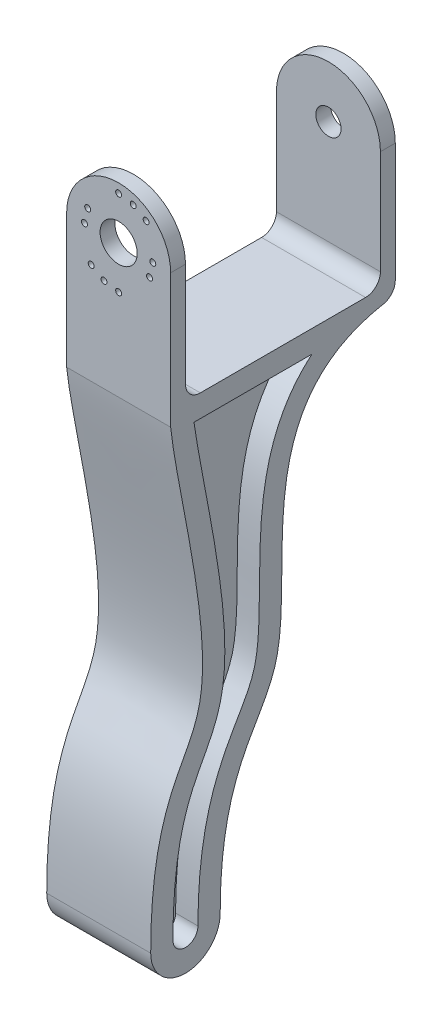
SolidWorks part; units mm, degrees
material "ABS"
ref_plane "Front Plane" through (0, 0, 0) normal (0, 0, 1) x (1, 0, 0)
ref_plane "Top Plane" through (0, 0, 0) normal (0, 1, 0) x (1, 0, 0)
ref_plane "Right Plane" through (0, 0, 0) normal (1, 0, 0) x (0, 0, -1)
sketch "Sketch1" plane through (0, 0, 0) normal (0, 1, 0) x (1, 0, 0)
  line L1 (0, 0) -> (-17.78, 0)
  line L2 (0, 0) -> (0, -33.3375)
  line L3 (0, -33.3375) -> (-17.78, -33.3375)
  line L4 (-17.78, 0) -> (-17.78, -33.3375)
  dimension "D1" = 17.78
  dimension "D2" = 33.3375
extrude "Boss-Extrude1" add sketch "Sketch1" along normal blind 2.54
sketch "Sketch2" plane through (0, 0, 33.3375) normal (0, 0, 1) x (1, 0, 0)
  line L0 (-17.78, 0) -> (0, 0) construction
  line L1 (-17.78, 2.54) -> (-17.78, 0) construction
  line L2 (-17.78, 0) -> (0, 0)
  line L3 (-17.78, 2.54) -> (-17.78, 0)
  line L4 (-17.78, 2.54) -> (-17.78, 22.86)
  line L5 (0, 22.86) -> (0, 2.54)
  line L6 (-17.78, 2.54) -> (0, 2.54) construction
  line L7 (-8.89, 30.1625) -> (-6.3887, 29.7208) construction
  line L8 (-6.3887, 29.7208) -> (-4.19, 28.449) construction
  line L9 (-3.048, 22.86) -> (-3.6002, 20.3807) construction
  line L10 (-8.89, 15.5575) -> (-11.3913, 15.9992) construction
  line L11 (-13.59, 17.271) -> (-11.3913, 15.9992) construction
  line L12 (-14.732, 22.86) -> (-14.1798, 25.3393) construction
  line L13 (0, 2.54) -> (0, 0)
  circle A0 centre (-8.89, 22.86) radius 8.89
  circle A1 centre (-8.89, 22.86) radius 8.89 construction
  circle A2 centre (-8.89, 22.86) radius 3.175
  circle A3 centre (-8.89, 22.86) radius 7.3025 construction
  circle A4 centre (-8.89, 22.86) radius 5.842 construction
  circle A5 centre (-8.89, 30.1625) radius 0.508
  circle A6 centre (-6.3887, 29.7208) radius 0.508
  circle A7 centre (-4.19, 28.449) radius 0.508
  circle A8 centre (-8.89, 15.5575) radius 0.508
  circle A9 centre (-11.3913, 15.9992) radius 0.508
  circle A10 centre (-13.59, 17.271) radius 0.508
  circle A11 centre (-3.048, 22.86) radius 0.508
  circle A12 centre (-3.6002, 20.3807) radius 0.508
  circle A13 centre (-14.732, 22.86) radius 0.508
  circle A14 centre (-14.1798, 25.3393) radius 0.508
  point P9 (-8.89, 2.54)
  line M3 (-17.78, 0) -> (0, 0)
  line M4 (0, 0) -> (0, 2.54)
  line M5 (0, 2.54) -> (-17.78, 2.54)
  line M6 (-17.78, 2.54) -> (-17.78, 0)
  dimension "D1" = 17.78
  dimension "D4" = 11.684
  dimension "D5" = 1.016
  dimension "D6" = 14.605
  dimension "D7" = 6.35
  dimension "D2" = 20.32
  dimension "D3" = 2.54
extrude "Boss-Extrude2" add sketch "Sketch2" along normal blind 2.54 contours A0 L4 M5 M4 | A0 | M6 M3 M4 M5 region at (-8.89, 1.27, 33.3375) region at (-8.89, 9.3565, 33.3375) region at (-8.89, 31.4986, 33.3375)
sketch "Sketch3" plane through (0, 0, 0) normal (0, 0, -1) x (-1, 0, 0)
  line L3 (0, 22.86) -> (0, 0)
  line L4 (17.78, 0) -> (17.78, 22.86)
  line L5 (0, 22.86) -> (0, 0)
  line L6 (0, 0) -> (17.78, 0)
  line L8 (17.78, 0) -> (17.78, 22.86)
  line L10 (0, 0) -> (17.78, 0)
  circle A0 centre (8.89, 22.86) radius 2.159
  arc A1 (17.78, 22.86) -> (0, 22.86) centre (8.89, 22.86) ccw
  arc A2 (17.78, 22.86) -> (0, 22.86) centre (8.89, 22.86) ccw
  dimension "D2" = 4.318
  dimension "D1" = 0
extrude "Boss-Extrude3" add sketch "Sketch3" along normal blind 2.54
sketch "Sketch7" plane through (-17.78, 0, 0) normal (-1, 0, 0) x (0, 0, 1)
  line L0 (-2.54, 0) -> (35.8775, 0) construction
  line L1 (-0.2642, 0) -> (35.8775, 0)
  arc A0 (39.2853, -76.2) -> (27.3979, -76.2) centre (33.3416, -76.2) cw
  spline S0 degree 3 poles (35.8775, 0) (34.7476, -10.4834) (23.9939, -49.6564) (39.2853, -53.149) (39.2853, -76.2) knots 0 0 0 0 0.561591 1 1 1 1
  spline S1 degree 3 poles (-0.2642, 0) (22.6993, -4.421) (9.1079, -48.9083) (27.3979, -54.2744) (27.3979, -76.2) knots 0 0 0 0 0.588388 1 1 1 1
  point P5 (16.5148, -21.1478)
  point P8 (17.7426, -43.2288)
  dimension "D1" = 76.2
extrude "Boss-Extrude5" add sketch "Sketch7" against normal up to vertex (17.78 mm away) up to point (0, 0, -2.54)
sketch "Sketch8" plane through (-17.78, 0, 0) normal (-1, 0, 0) x (0, 0, 1)
  line L14 (31.88, -1.27) -> (11.6921, -1.27)
  line L15 (31.88, -1.27) -> (11.6921, -1.27)
  arc A2 (31.2079, -76.2) -> (35.4753, -76.2) centre (33.3416, -76.2) ccw
  arc A3 (31.2079, -76.2) -> (35.4753, -76.2) centre (33.3416, -76.2) ccw
  spline S4 degree 3 poles (191.5387, 1159.5015) (-2624.3969, -2269.4747) (-135.4148, 154.7361) (13.7872, -3.2677) (14.0633, -3.5786) (14.5984, -4.2195) (14.8579, -4.5504) (16.0976, -6.2321) (16.9144, -7.6745) (17.9249, -9.9572) (18.2267, -10.7414) (18.7577, -12.3195) (18.9882, -13.1154) (19.5926, -15.5205) (19.88, -17.1468) (20.2993, -20.43) (20.4309, -22.0896) (20.5997, -25.4119) (20.6368, -27.0755) (20.6787, -30.4041) (20.6824, -32.0693) (20.7205, -34.5654) (20.7387, -35.3972) (20.8011, -37.0594) (20.8451, -37.8899) (20.9824, -39.5485) (21.0748, -40.3766) (21.2865, -41.6151) (21.37, -42.0294) (21.5727, -42.846) (21.6913, -43.2459) (22.3639, -45.2068) (23.1655, -46.6471) (24.4075, -48.7882) (24.8279, -49.4987) (25.6447, -50.9316) (26.0416, -51.6546) (27.1655, -53.846) (27.8235, -55.338) (28.9336, -58.3925) (29.3886, -59.9539) (30.1267, -63.1355) (30.4109, -64.7609) (30.8381, -68.0141) (30.9826, -69.6459) (37.3388, -182.0818) (-195.7435, -311.0325) (3017.6087, -178.6258) knots -8.141776 -8.141776 -8.141776 -8.141776 0.03125 0.03125 0.046875 0.046875 0.0625 0.0625 0.125 0.125 0.15625 0.15625 0.1875 0.1875 0.25 0.25 0.3125 0.3125 0.375 0.375 0.4375 0.4375 0.46875 0.46875 0.5 0.5 0.53125 0.53125 0.546875 0.546875 0.5625 0.5625 0.625 0.625 0.65625 0.65625 0.6875 0.6875 0.75 0.75 0.8125 0.8125 0.875 0.875 0.9375 0.9375 5.170963 5.170963 5.170963 5.170963 only from (11.6921, -1.27) to (31.2079, -76.2)
  spline S5 degree 3 poles (3024.2462, -54.6919) (-159.6653, -311.7203) (40.6316, -179.7506) (35.2875, -69.8173) (35.166, -68.2301) (34.7975, -65.0703) (34.551, -63.4976) (34.0399, -61.1547) (33.8457, -60.3765) (33.3985, -58.8268) (33.1465, -58.0599) (32.5843, -56.5559) (32.2732, -55.8171) (31.5986, -54.3627) (31.2348, -53.6471) (30.4847, -52.226) (30.099, -51.5199) (29.3533, -50.0976) (28.9941, -49.3812) (28.3416, -47.9234) (28.0484, -47.1819) (27.5467, -45.6667) (27.3381, -44.8931) (27.0911, -43.7075) (27.0197, -43.3073) (26.8973, -42.5092) (26.846, -42.1101) (26.7169, -40.9127) (26.6636, -40.1144) (26.5748, -37.7192) (26.609, -36.1222) (26.7855, -32.9278) (26.9291, -31.3289) (27.464, -26.5423) (27.9553, -23.3733) (29.0413, -17.0522) (29.6409, -13.901) (30.5319, -9.1728) (30.8277, -7.5966) (43.2523, 62.1585) (32.5985, 134.0797) (-2884.8445, 683.475) knots -4.190343 -4.190343 -4.190343 -4.190343 0.0625 0.0625 0.125 0.125 0.1875 0.1875 0.21875 0.21875 0.25 0.25 0.28125 0.28125 0.3125 0.3125 0.34375 0.34375 0.375 0.375 0.40625 0.40625 0.4375 0.4375 0.453125 0.453125 0.46875 0.46875 0.5 0.5 0.5625 0.5625 0.625 0.625 0.75 0.75 0.875 0.875 0.9375 0.9375 3.636636 3.636636 3.636636 3.636636 only from (35.4753, -76.2) to (31.88, -1.27)
  spline S6 degree 3 poles (11.6921, -1.27) (12.3295, -1.798) (12.9331, -2.3632) (13.7872, -3.2677) (14.0633, -3.5786) (14.5984, -4.2195) (14.8579, -4.5504) (16.0976, -6.2321) (16.9144, -7.6745) (17.9249, -9.9572) (18.2267, -10.7414) (18.7577, -12.3195) (18.9882, -13.1154) (19.5926, -15.5205) (19.88, -17.1468) (20.2993, -20.43) (20.4309, -22.0896) (20.5997, -25.4119) (20.6368, -27.0755) (20.6787, -30.4041) (20.6824, -32.0693) (20.7205, -34.5654) (20.7387, -35.3972) (20.8011, -37.0594) (20.8451, -37.8899) (20.9824, -39.5485) (21.0748, -40.3766) (21.2865, -41.6151) (21.37, -42.0294) (21.5727, -42.846) (21.6913, -43.2459) (22.3639, -45.2068) (23.1655, -46.6471) (24.4075, -48.7882) (24.8279, -49.4987) (25.6447, -50.9316) (26.0416, -51.6546) (27.1655, -53.846) (27.8235, -55.338) (28.9336, -58.3925) (29.3886, -59.9539) (30.1267, -63.1355) (30.4109, -64.7609) (30.8381, -68.0141) (30.9826, -69.6459) (31.1675, -72.9175) (31.2079, -74.5572) (31.2079, -76.2) knots 0 0 0 0 0.03125 0.03125 0.046875 0.046875 0.0625 0.0625 0.125 0.125 0.15625 0.15625 0.1875 0.1875 0.25 0.25 0.3125 0.3125 0.375 0.375 0.4375 0.4375 0.46875 0.46875 0.5 0.5 0.53125 0.53125 0.546875 0.546875 0.5625 0.5625 0.625 0.625 0.65625 0.65625 0.6875 0.6875 0.75 0.75 0.8125 0.8125 0.875 0.875 0.9375 0.9375 1 1 1 1
  spline S7 degree 3 poles (35.4753, -76.2) (35.4753, -74.5989) (35.4423, -73.0016) (35.2875, -69.8173) (35.166, -68.2301) (34.7975, -65.0703) (34.551, -63.4976) (34.0399, -61.1547) (33.8457, -60.3765) (33.3985, -58.8268) (33.1465, -58.0599) (32.5843, -56.5559) (32.2732, -55.8171) (31.5986, -54.3627) (31.2348, -53.6471) (30.4847, -52.226) (30.099, -51.5199) (29.3533, -50.0976) (28.9941, -49.3812) (28.3416, -47.9234) (28.0484, -47.1819) (27.5467, -45.6667) (27.3381, -44.8931) (27.0911, -43.7075) (27.0197, -43.3073) (26.8973, -42.5092) (26.846, -42.1101) (26.7169, -40.9127) (26.6636, -40.1144) (26.5748, -37.7192) (26.609, -36.1222) (26.7855, -32.9278) (26.9291, -31.3289) (27.464, -26.5423) (27.9553, -23.3733) (29.0413, -17.0522) (29.6409, -13.901) (30.5319, -9.1728) (30.8277, -7.5966) (31.3901, -4.4392) (31.659, -2.8586) (31.88, -1.27) knots 0 0 0 0 0.0625 0.0625 0.125 0.125 0.1875 0.1875 0.21875 0.21875 0.25 0.25 0.28125 0.28125 0.3125 0.3125 0.34375 0.34375 0.375 0.375 0.40625 0.40625 0.4375 0.4375 0.453125 0.453125 0.46875 0.46875 0.5 0.5 0.5625 0.5625 0.625 0.625 0.75 0.75 0.875 0.875 0.9375 0.9375 1 1 1 1
  dimension "D1" = 3.81
extrude "Cut-Extrude2" cut sketch "Sketch8" against normal blind 3.81
sketch "Sketch9" plane through (0, 0, 0) normal (1, 0, 0) x (0, 0, -1)
  line L14 (-11.6921, -1.27) -> (-31.88, -1.27)
  line L15 (-11.6921, -1.27) -> (-31.88, -1.27)
  arc A2 (-35.4753, -76.2) -> (-31.2079, -76.2) centre (-33.3416, -76.2) ccw
  arc A3 (-35.4753, -76.2) -> (-31.2079, -76.2) centre (-33.3416, -76.2) ccw
  spline S4 degree 3 poles (2886.0589, 678.5752) (-32.9091, 134.1861) (-43.2768, 62.2342) (-30.8184, -7.6475) (-30.52, -9.2365) (-29.6215, -14.0031) (-29.0175, -17.1799) (-28.1992, -21.9595) (-27.9407, -23.555) (-27.4702, -26.7536) (-27.258, -28.3566) (-26.9055, -31.5743) (-26.765, -33.1889) (-26.6001, -36.4133) (-26.5742, -38.0252) (-26.6837, -40.4424) (-26.7453, -41.2479) (-26.9386, -42.8587) (-27.0719, -43.6676) (-27.4276, -45.2405) (-27.6493, -46.009) (-28.1747, -47.5124) (-28.4784, -48.2473) (-29.4803, -50.4151) (-30.2719, -51.8096) (-31.3812, -53.9334) (-31.7373, -54.6479) (-32.3911, -56.0916) (-32.6896, -56.8211) (-33.4945, -59.0338) (-33.9113, -60.541) (-34.5682, -63.6029) (-34.8097, -65.1571) (-35.0813, -67.5128) (-35.1564, -68.3017) (-35.2804, -69.8786) (-35.3293, -70.6676) (-40.5176, -178.6516) (155.4531, -295.2545) (-3019.3256, -254.1737) knots -2.619498 -2.619498 -2.619498 -2.619498 0.0625 0.0625 0.125 0.125 0.25 0.25 0.3125 0.3125 0.375 0.375 0.4375 0.4375 0.5 0.5 0.53125 0.53125 0.5625 0.5625 0.59375 0.59375 0.625 0.625 0.6875 0.6875 0.71875 0.71875 0.75 0.75 0.8125 0.8125 0.875 0.875 0.90625 0.90625 0.9375 0.9375 5.180233 5.180233 5.180233 5.180233 only from (-31.88, -1.27) to (-35.4753, -76.2)
  spline S5 degree 3 poles (-3018.8985, -50.7657) (199.9243, -324.5572) (-37.3532, -183.3144) (-30.9863, -69.6981) (-30.8445, -68.083) (-30.4275, -64.8688) (-30.1523, -63.2697) (-29.4258, -60.0927) (-28.9701, -58.5078) (-27.8644, -55.4368) (-27.2112, -53.945) (-26.1002, -51.7644) (-25.7086, -51.0468) (-24.9001, -49.6226) (-24.4829, -48.9161) (-23.2464, -46.79) (-22.4426, -45.3638) (-21.755, -43.4444) (-21.6329, -43.0539) (-21.422, -42.2585) (-21.3338, -41.8533) (-21.1832, -41.032) (-21.1203, -40.6148) (-21.014, -39.7819) (-20.9703, -39.3651) (-20.8594, -38.1139) (-20.812, -37.2787) (-20.7445, -35.6072) (-20.7247, -34.7709) (-20.6835, -32.2613) (-20.6798, -30.5873) (-20.6199, -25.5672) (-20.5202, -22.2251) (-20.0019, -18.0866) (-19.8783, -17.2608) (-19.5815, -15.6141) (-19.4077, -14.7911) (-18.7979, -12.3462) (-18.2774, -10.7603) (-17.2678, -8.4698) (-16.8931, -7.721) (-16.0551, -6.2576) (-15.5976, -5.5537) (35.5838, 63.8587) (476.5986, -213.2694) (2388.4713, -1793.7355) knots -4.255042 -4.255042 -4.255042 -4.255042 0.0625 0.0625 0.125 0.125 0.1875 0.1875 0.25 0.25 0.3125 0.3125 0.34375 0.34375 0.375 0.375 0.4375 0.4375 0.453125 0.453125 0.46875 0.46875 0.484375 0.484375 0.5 0.5 0.53125 0.53125 0.5625 0.5625 0.625 0.625 0.75 0.75 0.78125 0.78125 0.8125 0.8125 0.875 0.875 0.90625 0.90625 0.9375 0.9375 4.147931 4.147931 4.147931 4.147931 only from (-31.2079, -76.2) to (-11.6921, -1.27)
  spline S6 degree 3 poles (-31.88, -1.27) (-31.6573, -2.8713) (-31.3858, -4.4647) (-30.8184, -7.6475) (-30.52, -9.2365) (-29.6215, -14.0031) (-29.0175, -17.1799) (-28.1992, -21.9595) (-27.9407, -23.555) (-27.4702, -26.7536) (-27.258, -28.3566) (-26.9055, -31.5743) (-26.765, -33.1889) (-26.6001, -36.4133) (-26.5742, -38.0252) (-26.6837, -40.4424) (-26.7453, -41.2479) (-26.9386, -42.8587) (-27.0719, -43.6676) (-27.4276, -45.2405) (-27.6493, -46.009) (-28.1747, -47.5124) (-28.4784, -48.2473) (-29.4803, -50.4151) (-30.2719, -51.8096) (-31.3812, -53.9334) (-31.7373, -54.6479) (-32.3911, -56.0916) (-32.6896, -56.8211) (-33.4945, -59.0338) (-33.9113, -60.541) (-34.5682, -63.6029) (-34.8097, -65.1571) (-35.0813, -67.5128) (-35.1564, -68.3017) (-35.2804, -69.8786) (-35.3293, -70.6676) (-35.4431, -73.0362) (-35.4753, -74.6174) (-35.4753, -76.2) knots 0 0 0 0 0.0625 0.0625 0.125 0.125 0.25 0.25 0.3125 0.3125 0.375 0.375 0.4375 0.4375 0.5 0.5 0.53125 0.53125 0.5625 0.5625 0.59375 0.59375 0.625 0.625 0.6875 0.6875 0.71875 0.71875 0.75 0.75 0.8125 0.8125 0.875 0.875 0.90625 0.90625 0.9375 0.9375 1 1 1 1
  spline S7 degree 3 poles (-31.2079, -76.2) (-31.2079, -74.5679) (-31.168, -72.9405) (-30.9863, -69.6981) (-30.8445, -68.083) (-30.4275, -64.8688) (-30.1523, -63.2697) (-29.4258, -60.0927) (-28.9701, -58.5078) (-27.8644, -55.4368) (-27.2112, -53.945) (-26.1002, -51.7644) (-25.7086, -51.0468) (-24.9001, -49.6226) (-24.4829, -48.9161) (-23.2464, -46.79) (-22.4426, -45.3638) (-21.755, -43.4444) (-21.6329, -43.0539) (-21.422, -42.2585) (-21.3338, -41.8533) (-21.1832, -41.032) (-21.1203, -40.6148) (-21.014, -39.7819) (-20.9703, -39.3651) (-20.8594, -38.1139) (-20.812, -37.2787) (-20.7445, -35.6072) (-20.7247, -34.7709) (-20.6835, -32.2613) (-20.6798, -30.5873) (-20.6199, -25.5672) (-20.5202, -22.2251) (-20.0019, -18.0866) (-19.8783, -17.2608) (-19.5815, -15.6141) (-19.4077, -14.7911) (-18.7979, -12.3462) (-18.2774, -10.7603) (-17.2678, -8.4698) (-16.8931, -7.721) (-16.0551, -6.2576) (-15.5976, -5.5537) (-14.1174, -3.5462) (-12.9827, -2.339) (-11.6921, -1.27) knots 0 0 0 0 0.0625 0.0625 0.125 0.125 0.1875 0.1875 0.25 0.25 0.3125 0.3125 0.34375 0.34375 0.375 0.375 0.4375 0.4375 0.453125 0.453125 0.46875 0.46875 0.484375 0.484375 0.5 0.5 0.53125 0.53125 0.5625 0.5625 0.625 0.625 0.75 0.75 0.78125 0.78125 0.8125 0.8125 0.875 0.875 0.90625 0.90625 0.9375 0.9375 1 1 1 1
  dimension "D1" = 3.81
extrude "Cut-Extrude3" cut sketch "Sketch9" against normal blind 3.81
fillet "Fillet1" radius 2.54 3 edges at (-8.89, 0, -2.54) (-8.89, 2.54, 33.3375) (-8.89, 2.54, 0)
